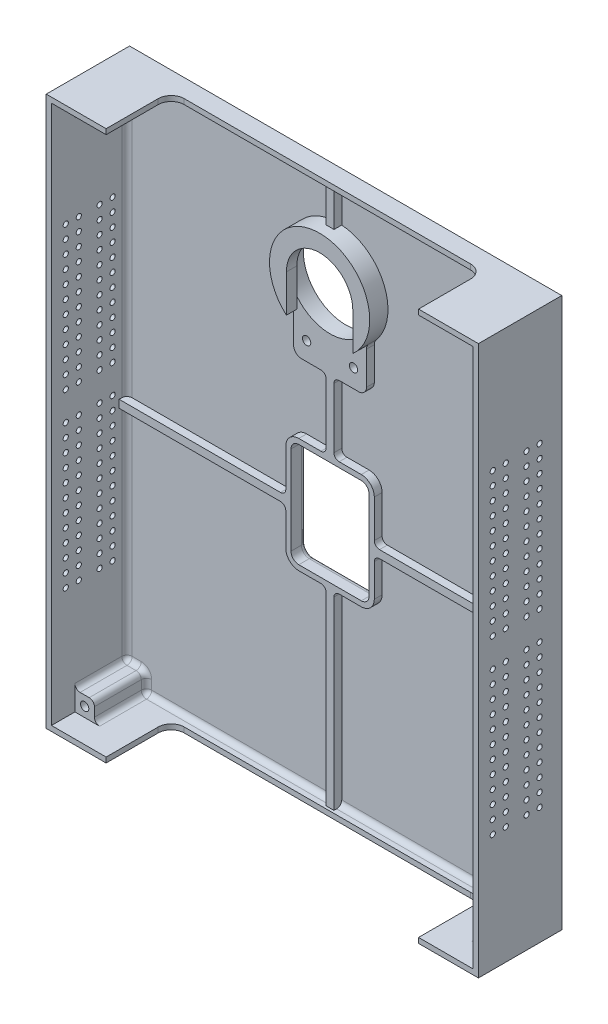
SolidWorks part; units mm, degrees
ref_plane "Front Plane" through (0, 0, 0) normal (0, 0, 1) x (1, 0, 0)
ref_plane "Top Plane" through (0, 0, 0) normal (0, 1, 0) x (1, 0, 0)
ref_plane "Right Plane" through (0, 0, 0) normal (1, 0, 0) x (0, 0, -1)
ref_plane "Plane1" through (0, 0, -1) normal (0, 0, 1) x (1, 0, 0)
sketch "Sketch5" plane through (0, 0, -1) normal (0, 0, 1) x (1, 0, 0)
  line L0 (100, 83.2573) -> (100, -169.2647) construction
  line L2 (17, 83.2573) -> (17, -127.7573)
  line L3 (17, -127.7573) -> (183, -127.7573)
  line L4 (183, 83.2573) -> (183, -127.7573)
  line L5 (17, 83.2573) -> (183, 83.2573)
  circle A0 centre (100, 48.2573) radius 16.25
  point P17 (45, 83.2573)
  dimension "D1" = 166
  dimension "D2" = 83
extrude "Boss-Extrude5" add sketch "Sketch5" along normal blind 3
sketch "Sketch6" plane through (0, 0, 2) normal (0, 0, 1) x (1, 0, 0)
  line L0 (116.25, 48.2573) -> (83.75, 48.2573) construction
  line L2 (86, 35.0451) -> (86, 18.2573)
  line L3 (86, 18.2573) -> (114, 18.2573)
  line L4 (114, 35.0451) -> (114, 18.2573)
  line L5 (100, 48.2573) -> (100, 52.872) construction
  circle A1 centre (100, 48.2573) radius 16.25
  arc A2 (114, 35.0451) -> (86, 35.0451) centre (100, 48.2573) ccw
  circle A6 centre (100, 48.2573) radius 16.25 construction
extrude "Boss-Extrude6" add sketch "Sketch6" along normal blind 3
sketch "Sketch7" plane through (0, 0, 5) normal (0, 0, 1) x (1, 0, 0)
  line L0 (112.75, 33.8351) -> (112.75, 48.2573)
  line L2 (87.25, 48.2573) -> (87.25, 33.8351)
  line L3 (100, 64.5073) -> (100, 48.2573) construction
  line L4 (100, 48.2573) -> (116.25, 48.2573) construction
  arc A8 (112.75, 33.8351) -> (87.25, 33.8351) centre (100, 48.2573) ccw
  circle A9 centre (100, 48.2573) radius 19.25 construction
  circle A10 centre (100, 48.2573) radius 16.25 construction
  circle A12 centre (100, 48.2573) radius 12.75
  arc A13 (112.75, 48.2573) -> (87.25, 48.2573) centre (100, 48.2573) ccw
  dimension "D1" = 1
extrude "Boss-Extrude7" add sketch "Sketch7" along normal blind 4
sketch "Sketch8" plane through (0, 0, 2) normal (0, 0, 1) x (1, 0, 0)
  line L4 (17, -127.7573) -> (183, -127.7573)
  line L5 (183, -127.7573) -> (183, 83.2573)
  line L6 (183, 83.2573) -> (17, 83.2573)
  line L7 (17, 83.2573) -> (17, -127.7573)
  line L8 (17, -127.7573) -> (183, -127.7573)
  line L9 (183, -127.7573) -> (183, 83.2573)
  line L10 (183, 83.2573) -> (17, 83.2573)
  line L11 (17, 83.2573) -> (17, -127.7573)
  line L12 (19, -125.7573) -> (181, -125.7573)
  line L13 (181, -125.7573) -> (181, 81.2573)
  line L14 (181, 81.2573) -> (19, 81.2573)
  line L15 (19, 81.2573) -> (19, -125.7573)
  dimension "D1" = 0
  dimension "D2" = 2
extrude "Boss-Extrude8" add sketch "Sketch8" along normal blind 29
fillet "Fillet2" radius 3 4 edges at (114, 18.2573, 3.5) (114, 35.0451, 3.5) (86, 18.2573, 3.5) (86, 35.0451, 3.5)
sketch "Sketch9" plane through (0, 0, 5) normal (0, 0, 1) x (1, 0, 0)
  line L0 (100, 48.2573) -> (100, 25.2573) construction
  line L1 (91, 25.2573) -> (109, 25.2573) construction
  line L2 (100, 25.2573) -> (100, 23.2329) construction
  circle A0 centre (91, 25.2573) radius 1.6
  circle A1 centre (109, 25.2573) radius 1.6
extrude "Cut-Extrude1" cut sketch "Sketch9" against normal up to surface (6 mm away) up to face at (100, -22.25, -1)
sketch "Sketch12" plane through (183, 0, 0) normal (1, 0, 0) x (0, 0, -1)
  circle A0 centre (-12.5, -16.7427) radius 1
  circle A1 centre (-7.5, -16.7427) radius 1
  circle A2 centre (-7.5, -11.7427) radius 1
  circle A3 centre (-7.5, -6.7427) radius 1
  circle A4 centre (-7.5, -1.7427) radius 1
  circle A5 centre (-7.5, 3.2573) radius 1
  circle A6 centre (-7.5, 8.2573) radius 1
  circle A7 centre (-7.5, 13.2573) radius 1
  circle A8 centre (-7.5, 18.2573) radius 1
  circle A9 centre (-7.5, 23.2573) radius 1
  circle A10 centre (-7.5, 28.2573) radius 1
  circle A11 centre (-7.5, 33.2573) radius 1
  circle A12 centre (-7.5, 38.2573) radius 1
  circle A13 centre (-12.5, -11.7427) radius 1
  circle A14 centre (-12.5, -6.7427) radius 1
  circle A15 centre (-12.5, -1.7427) radius 1
  circle A16 centre (-12.5, 3.2573) radius 1
  circle A17 centre (-12.5, 8.2573) radius 1
  circle A18 centre (-12.5, 13.2573) radius 1
  circle A19 centre (-12.5, 18.2573) radius 1
  circle A20 centre (-12.5, 23.2573) radius 1
  circle A21 centre (-12.5, 28.2573) radius 1
  circle A22 centre (-12.5, 33.2573) radius 1
  circle A23 centre (-12.5, 38.2573) radius 1
  circle A24 centre (-12.5, -82.7573) radius 1
  circle A25 centre (-12.5, -77.7573) radius 1
  circle A26 centre (-12.5, -72.7573) radius 1
  circle A27 centre (-12.5, -67.7573) radius 1
  circle A28 centre (-12.5, -62.7573) radius 1
  circle A29 centre (-12.5, -57.7573) radius 1
  circle A30 centre (-12.5, -52.7573) radius 1
  circle A31 centre (-12.5, -47.7573) radius 1
  circle A32 centre (-12.5, -42.7573) radius 1
  circle A33 centre (-12.5, -37.7573) radius 1
  circle A34 centre (-12.5, -32.7573) radius 1
  circle A35 centre (-7.5, -82.7573) radius 1
  circle A36 centre (-7.5, -77.7573) radius 1
  circle A37 centre (-7.5, -72.7573) radius 1
  circle A38 centre (-7.5, -67.7573) radius 1
  circle A39 centre (-7.5, -62.7573) radius 1
  circle A40 centre (-7.5, -57.7573) radius 1
  circle A41 centre (-7.5, -52.7573) radius 1
  circle A42 centre (-7.5, -47.7573) radius 1
  circle A43 centre (-7.5, -42.7573) radius 1
  circle A44 centre (-7.5, -37.7573) radius 1
  circle A45 centre (-7.5, -32.7573) radius 1
  circle A46 centre (-7.5, -27.7573) radius 1
  circle A47 centre (-12.5, -27.7573) radius 1
  circle A48 centre (-20.5, -27.7573) radius 1
  circle A49 centre (-25.5, -27.7573) radius 1
  circle A50 centre (-25.5, -32.7573) radius 1
  circle A51 centre (-25.5, -37.7573) radius 1
  circle A52 centre (-25.5, -42.7573) radius 1
  circle A53 centre (-25.5, -47.7573) radius 1
  circle A54 centre (-25.5, -52.7573) radius 1
  circle A55 centre (-25.5, -57.7573) radius 1
  circle A56 centre (-25.5, -62.7573) radius 1
  circle A57 centre (-25.5, -67.7573) radius 1
  circle A58 centre (-25.5, -72.7573) radius 1
  circle A59 centre (-25.5, -77.7573) radius 1
  circle A60 centre (-25.5, -82.7573) radius 1
  circle A61 centre (-20.5, -32.7573) radius 1
  circle A62 centre (-20.5, -37.7573) radius 1
  circle A63 centre (-20.5, -42.7573) radius 1
  circle A64 centre (-20.5, -47.7573) radius 1
  circle A65 centre (-20.5, -52.7573) radius 1
  circle A66 centre (-20.5, -57.7573) radius 1
  circle A67 centre (-20.5, -62.7573) radius 1
  circle A68 centre (-20.5, -67.7573) radius 1
  circle A69 centre (-20.5, -72.7573) radius 1
  circle A70 centre (-20.5, -77.7573) radius 1
  circle A71 centre (-20.5, -82.7573) radius 1
  circle A72 centre (-20.5, 38.2573) radius 1
  circle A73 centre (-20.5, 33.2573) radius 1
  circle A74 centre (-20.5, 28.2573) radius 1
  circle A75 centre (-20.5, 23.2573) radius 1
  circle A76 centre (-20.5, 18.2573) radius 1
  circle A77 centre (-20.5, 13.2573) radius 1
  circle A78 centre (-20.5, 8.2573) radius 1
  circle A79 centre (-20.5, 3.2573) radius 1
  circle A80 centre (-20.5, -1.7427) radius 1
  circle A81 centre (-20.5, -6.7427) radius 1
  circle A82 centre (-20.5, -11.7427) radius 1
  circle A83 centre (-25.5, 38.2573) radius 1
  circle A84 centre (-25.5, 33.2573) radius 1
  circle A85 centre (-25.5, 28.2573) radius 1
  circle A86 centre (-25.5, 23.2573) radius 1
  circle A87 centre (-25.5, 18.2573) radius 1
  circle A88 centre (-25.5, 13.2573) radius 1
  circle A89 centre (-25.5, 8.2573) radius 1
  circle A90 centre (-25.5, 3.2573) radius 1
  circle A91 centre (-25.5, -1.7427) radius 1
  circle A92 centre (-25.5, -6.7427) radius 1
  circle A93 centre (-25.5, -11.7427) radius 1
  circle A94 centre (-25.5, -16.7427) radius 1
  circle A95 centre (-20.5, -16.7427) radius 1
  dimension "D1" = 2
  dimension "D2" = 12
extrude "Cut-Extrude4" cut sketch "Sketch12" against normal up to surface (2 mm away) up to face at (181, -22.25, 16.5)
sketch "Sketch13" plane through (0, 0, -1) normal (0, 0, -1) x (-1, 0, 0)
  line L0 (-183, -30.7808) -> (-100, -30.7808) construction
  line L1 (-183, -127.7573) -> (-183, 83.2573) construction
  line L6 (-100, 83.2573) -> (-100, -30.7808) construction
  line L7 (-183, 83.2573) -> (-17, 83.2573) construction
  line L14 (-85, -47.7808) -> (-85, -13.7808)
  line L15 (-88, -10.7808) -> (-112, -10.7808)
  line L16 (-115, -13.7808) -> (-115, -47.7808)
  line L17 (-112, -50.7808) -> (-88, -50.7808)
  circle A1 centre (-100, -30.7808) radius 9 construction
  arc A15 (-88, -50.7808) -> (-85, -47.7808) centre (-88, -47.7808) ccw
  arc A16 (-85, -13.7808) -> (-88, -10.7808) centre (-88, -13.7808) ccw
  arc A17 (-112, -10.7808) -> (-115, -13.7808) centre (-112, -13.7808) ccw
  arc A18 (-115, -47.7808) -> (-112, -50.7808) centre (-112, -47.7808) ccw
extrude "Cut-Extrude5" cut sketch "Sketch13" against normal blind 3
sketch "Sketch14" plane through (17, 0, 0) normal (-1, 0, 0) x (0, 0, 1)
  circle A1 centre (12.5, -82.7573) radius 1
  circle A2 centre (12.5, -82.7573) radius 1
  circle A3 centre (12.5, -16.7427) radius 1
  circle A4 centre (12.5, -16.7427) radius 1
  circle A5 centre (7.5, 18.2573) radius 1
  circle A6 centre (7.5, 18.2573) radius 1
  circle A7 centre (7.5, 13.2573) radius 1
  circle A8 centre (7.5, 13.2573) radius 1
  circle A9 centre (7.5, 8.2573) radius 1
  circle A10 centre (7.5, 8.2573) radius 1
  circle A11 centre (7.5, 3.2573) radius 1
  circle A12 centre (7.5, 3.2573) radius 1
  circle A13 centre (7.5, -1.7427) radius 1
  circle A14 centre (7.5, -1.7427) radius 1
  circle A15 centre (7.5, -6.7427) radius 1
  circle A16 centre (7.5, -6.7427) radius 1
  circle A17 centre (7.5, -11.7427) radius 1
  circle A18 centre (7.5, -11.7427) radius 1
  circle A19 centre (7.5, -16.7427) radius 1
  circle A20 centre (7.5, -16.7427) radius 1
  circle A21 centre (12.5, 3.2573) radius 1
  circle A22 centre (12.5, 3.2573) radius 1
  circle A23 centre (12.5, -1.7427) radius 1
  circle A24 centre (12.5, -1.7427) radius 1
  circle A25 centre (12.5, -6.7427) radius 1
  circle A26 centre (12.5, -6.7427) radius 1
  circle A27 centre (12.5, -11.7427) radius 1
  circle A28 centre (12.5, -11.7427) radius 1
  circle A29 centre (7.5, 38.2573) radius 1
  circle A30 centre (7.5, 38.2573) radius 1
  circle A31 centre (7.5, 33.2573) radius 1
  circle A32 centre (7.5, 33.2573) radius 1
  circle A33 centre (7.5, 28.2573) radius 1
  circle A34 centre (7.5, 28.2573) radius 1
  circle A35 centre (7.5, 23.2573) radius 1
  circle A36 centre (7.5, 23.2573) radius 1
  circle A37 centre (12.5, -77.7573) radius 1
  circle A38 centre (12.5, -77.7573) radius 1
  circle A39 centre (12.5, 38.2573) radius 1
  circle A40 centre (12.5, 38.2573) radius 1
  circle A41 centre (12.5, 33.2573) radius 1
  circle A42 centre (12.5, 33.2573) radius 1
  circle A43 centre (12.5, 28.2573) radius 1
  circle A44 centre (12.5, 28.2573) radius 1
  circle A45 centre (12.5, 23.2573) radius 1
  circle A46 centre (12.5, 23.2573) radius 1
  circle A47 centre (12.5, 18.2573) radius 1
  circle A48 centre (12.5, 18.2573) radius 1
  circle A49 centre (12.5, 13.2573) radius 1
  circle A50 centre (12.5, 13.2573) radius 1
  circle A51 centre (12.5, 8.2573) radius 1
  circle A52 centre (12.5, 8.2573) radius 1
  circle A53 centre (12.5, -37.7573) radius 1
  circle A54 centre (12.5, -37.7573) radius 1
  circle A55 centre (12.5, -42.7573) radius 1
  circle A56 centre (12.5, -42.7573) radius 1
  circle A57 centre (12.5, -47.7573) radius 1
  circle A58 centre (12.5, -47.7573) radius 1
  circle A59 centre (12.5, -52.7573) radius 1
  circle A60 centre (12.5, -52.7573) radius 1
  circle A61 centre (12.5, -57.7573) radius 1
  circle A62 centre (12.5, -57.7573) radius 1
  circle A63 centre (12.5, -62.7573) radius 1
  circle A64 centre (12.5, -62.7573) radius 1
  circle A65 centre (12.5, -67.7573) radius 1
  circle A66 centre (12.5, -67.7573) radius 1
  circle A67 centre (12.5, -72.7573) radius 1
  circle A68 centre (12.5, -72.7573) radius 1
  circle A69 centre (7.5, -52.7573) radius 1
  circle A70 centre (7.5, -52.7573) radius 1
  circle A71 centre (7.5, -57.7573) radius 1
  circle A72 centre (7.5, -57.7573) radius 1
  circle A73 centre (7.5, -62.7573) radius 1
  circle A74 centre (7.5, -62.7573) radius 1
  circle A75 centre (7.5, -67.7573) radius 1
  circle A76 centre (7.5, -67.7573) radius 1
  circle A77 centre (7.5, -72.7573) radius 1
  circle A78 centre (7.5, -72.7573) radius 1
  circle A79 centre (7.5, -77.7573) radius 1
  circle A80 centre (7.5, -77.7573) radius 1
  circle A81 centre (7.5, -82.7573) radius 1
  circle A82 centre (7.5, -82.7573) radius 1
  circle A83 centre (12.5, -32.7573) radius 1
  circle A84 centre (12.5, -32.7573) radius 1
  circle A85 centre (25.5, -27.7573) radius 1
  circle A86 centre (25.5, -27.7573) radius 1
  circle A87 centre (20.5, -27.7573) radius 1
  circle A88 centre (20.5, -27.7573) radius 1
  circle A89 centre (12.5, -27.7573) radius 1
  circle A90 centre (12.5, -27.7573) radius 1
  circle A91 centre (7.5, -27.7573) radius 1
  circle A92 centre (7.5, -27.7573) radius 1
  circle A93 centre (7.5, -32.7573) radius 1
  circle A94 centre (7.5, -32.7573) radius 1
  circle A95 centre (7.5, -37.7573) radius 1
  circle A96 centre (7.5, -37.7573) radius 1
  circle A97 centre (7.5, -42.7573) radius 1
  circle A98 centre (7.5, -42.7573) radius 1
  circle A99 centre (7.5, -47.7573) radius 1
  circle A100 centre (7.5, -47.7573) radius 1
  circle A101 centre (25.5, -67.7573) radius 1
  circle A102 centre (25.5, -67.7573) radius 1
  circle A103 centre (25.5, -62.7573) radius 1
  circle A104 centre (25.5, -62.7573) radius 1
  circle A105 centre (25.5, -57.7573) radius 1
  circle A106 centre (25.5, -57.7573) radius 1
  circle A107 centre (25.5, -52.7573) radius 1
  circle A108 centre (25.5, -52.7573) radius 1
  circle A109 centre (25.5, -47.7573) radius 1
  circle A110 centre (25.5, -47.7573) radius 1
  circle A111 centre (25.5, -42.7573) radius 1
  circle A112 centre (25.5, -42.7573) radius 1
  circle A113 centre (25.5, -37.7573) radius 1
  circle A114 centre (25.5, -37.7573) radius 1
  circle A115 centre (25.5, -32.7573) radius 1
  circle A116 centre (25.5, -32.7573) radius 1
  circle A117 centre (20.5, -52.7573) radius 1
  circle A118 centre (20.5, -52.7573) radius 1
  circle A119 centre (20.5, -47.7573) radius 1
  circle A120 centre (20.5, -47.7573) radius 1
  circle A121 centre (20.5, -42.7573) radius 1
  circle A122 centre (20.5, -42.7573) radius 1
  circle A123 centre (20.5, -37.7573) radius 1
  circle A124 centre (20.5, -37.7573) radius 1
  circle A125 centre (20.5, -32.7573) radius 1
  circle A126 centre (20.5, -32.7573) radius 1
  circle A127 centre (25.5, -82.7573) radius 1
  circle A128 centre (25.5, -82.7573) radius 1
  circle A129 centre (25.5, -77.7573) radius 1
  circle A130 centre (25.5, -77.7573) radius 1
  circle A131 centre (25.5, -72.7573) radius 1
  circle A132 centre (25.5, -72.7573) radius 1
  circle A133 centre (20.5, 33.2573) radius 1
  circle A134 centre (20.5, 33.2573) radius 1
  circle A135 centre (20.5, 38.2573) radius 1
  circle A136 centre (20.5, 38.2573) radius 1
  circle A137 centre (20.5, -82.7573) radius 1
  circle A138 centre (20.5, -82.7573) radius 1
  circle A139 centre (20.5, -77.7573) radius 1
  circle A140 centre (20.5, -77.7573) radius 1
  circle A141 centre (20.5, -72.7573) radius 1
  circle A142 centre (20.5, -72.7573) radius 1
  circle A143 centre (20.5, -67.7573) radius 1
  circle A144 centre (20.5, -67.7573) radius 1
  circle A145 centre (20.5, -62.7573) radius 1
  circle A146 centre (20.5, -62.7573) radius 1
  circle A147 centre (20.5, -57.7573) radius 1
  circle A148 centre (20.5, -57.7573) radius 1
  circle A149 centre (20.5, -6.7427) radius 1
  circle A150 centre (20.5, -6.7427) radius 1
  circle A151 centre (20.5, -1.7427) radius 1
  circle A152 centre (20.5, -1.7427) radius 1
  circle A153 centre (20.5, 3.2573) radius 1
  circle A154 centre (20.5, 3.2573) radius 1
  circle A155 centre (20.5, 8.2573) radius 1
  circle A156 centre (20.5, 8.2573) radius 1
  circle A157 centre (20.5, 13.2573) radius 1
  circle A158 centre (20.5, 13.2573) radius 1
  circle A159 centre (20.5, 18.2573) radius 1
  circle A160 centre (20.5, 18.2573) radius 1
  circle A161 centre (20.5, 23.2573) radius 1
  circle A162 centre (20.5, 23.2573) radius 1
  circle A163 centre (20.5, 28.2573) radius 1
  circle A164 centre (20.5, 28.2573) radius 1
  circle A165 centre (25.5, 8.2573) radius 1
  circle A166 centre (25.5, 8.2573) radius 1
  circle A167 centre (25.5, 13.2573) radius 1
  circle A168 centre (25.5, 13.2573) radius 1
  circle A169 centre (25.5, 18.2573) radius 1
  circle A170 centre (25.5, 18.2573) radius 1
  circle A171 centre (25.5, 23.2573) radius 1
  circle A172 centre (25.5, 23.2573) radius 1
  circle A173 centre (25.5, 28.2573) radius 1
  circle A174 centre (25.5, 28.2573) radius 1
  circle A175 centre (25.5, 33.2573) radius 1
  circle A176 centre (25.5, 33.2573) radius 1
  circle A177 centre (25.5, 38.2573) radius 1
  circle A178 centre (25.5, 38.2573) radius 1
  circle A179 centre (20.5, -11.7427) radius 1
  circle A180 centre (20.5, -11.7427) radius 1
  circle A181 centre (20.5, -16.7427) radius 1
  circle A182 centre (20.5, -16.7427) radius 1
  circle A183 centre (25.5, -16.7427) radius 1
  circle A184 centre (25.5, -16.7427) radius 1
  circle A185 centre (25.5, -11.7427) radius 1
  circle A186 centre (25.5, -11.7427) radius 1
  circle A187 centre (25.5, -6.7427) radius 1
  circle A188 centre (25.5, -6.7427) radius 1
  circle A189 centre (25.5, -1.7427) radius 1
  circle A190 centre (25.5, -1.7427) radius 1
  circle A191 centre (25.5, 3.2573) radius 1
  circle A192 centre (25.5, 3.2573) radius 1
  dimension "D1" = 0
  dimension "D2" = 0
  dimension "D3" = 0
  dimension "D4" = 0
  dimension "D5" = 0
  dimension "D6" = 0
  dimension "D7" = 0
  dimension "D8" = 0
  dimension "D9" = 0
  dimension "D10" = 0
  dimension "D11" = 0
  dimension "D12" = 0
  dimension "D13" = 0
  dimension "D14" = 0
  dimension "D15" = 0
  dimension "D16" = 0
  dimension "D17" = 0
  dimension "D18" = 0
  dimension "D19" = 0
  dimension "D20" = 0
  dimension "D21" = 0
  dimension "D22" = 0
  dimension "D23" = 0
  dimension "D24" = 0
  dimension "D25" = 0
  dimension "D26" = 0
  dimension "D27" = 0
  dimension "D28" = 0
  dimension "D29" = 0
  dimension "D30" = 0
  dimension "D31" = 0
  dimension "D32" = 0
  dimension "D33" = 0
  dimension "D34" = 0
  dimension "D35" = 0
  dimension "D36" = 0
  dimension "D37" = 0
  dimension "D38" = 0
  dimension "D39" = 0
  dimension "D40" = 0
  dimension "D41" = 0
  dimension "D42" = 0
  dimension "D43" = 0
  dimension "D44" = 0
  dimension "D45" = 0
  dimension "D46" = 0
  dimension "D47" = 0
  dimension "D48" = 0
  dimension "D49" = 0
  dimension "D50" = 0
  dimension "D51" = 0
  dimension "D52" = 0
  dimension "D53" = 0
  dimension "D54" = 0
  dimension "D55" = 0
  dimension "D56" = 0
  dimension "D57" = 0
  dimension "D58" = 0
  dimension "D59" = 0
  dimension "D60" = 0
  dimension "D61" = 0
  dimension "D62" = 0
  dimension "D63" = 0
  dimension "D64" = 0
  dimension "D65" = 0
  dimension "D66" = 0
  dimension "D67" = 0
  dimension "D68" = 0
  dimension "D69" = 0
  dimension "D70" = 0
  dimension "D71" = 0
  dimension "D72" = 0
  dimension "D73" = 0
  dimension "D74" = 0
  dimension "D75" = 0
  dimension "D76" = 0
  dimension "D77" = 0
  dimension "D78" = 0
  dimension "D79" = 0
  dimension "D80" = 0
  dimension "D81" = 0
  dimension "D82" = 0
  dimension "D83" = 0
  dimension "D84" = 0
  dimension "D85" = 0
  dimension "D86" = 0
  dimension "D87" = 0
  dimension "D88" = 0
  dimension "D89" = 0
  dimension "D90" = 0
  dimension "D91" = 0
  dimension "D92" = 0
  dimension "D93" = 0
  dimension "D94" = 0
  dimension "D95" = 0
  dimension "D96" = 0
extrude "Cut-Extrude6" cut sketch "Sketch14" against normal up to surface (2 mm away) up to face at (19, -22.25, 16.5)
sketch "Sketch15" plane through (0, -127.7573, 0) normal (0, -1, 0) x (1, 0, 0)
  line L5 (100, -1) -> (100, 31) construction
  line L6 (17, -1) -> (183, -1) construction
  line L7 (17, 31) -> (183, 31) construction
  line L8 (40, 31) -> (160, 31)
  line L9 (40, 31) -> (40, 11)
  line L10 (45, 6) -> (155, 6)
  line L11 (160, 31) -> (160, 11)
  arc A4 (155, 6) -> (160, 11) centre (155, 11) ccw
  arc A5 (40, 11) -> (45, 6) centre (45, 11) ccw
  point P12 (160, 6)
  point P15 (40, 6)
  dimension "D4" = 5
  dimension "D1" = 60
  dimension "D2" = 120
  dimension "D3" = 25
extrude "Cut-Extrude7" cut sketch "Sketch15" against normal up to surface (2 mm away) up to face at (100, -125.7573, 16.5)
sketch "Sketch16" plane through (0, 83.2573, 0) normal (0, 1, 0) x (1, 0, 0)
  line L4 (40, -31) -> (160, -31)
  line L5 (40, -31) -> (160, -31)
  line L6 (160, -31) -> (160, -11)
  line L7 (160, -31) -> (160, -11)
  line L12 (155, -6) -> (45, -6)
  line L13 (155, -6) -> (45, -6)
  line L14 (40, -11) -> (40, -31)
  line L15 (40, -11) -> (40, -31)
  arc A2 (160, -11) -> (155, -6) centre (155, -11) ccw
  arc A3 (160, -11) -> (155, -6) centre (155, -11) ccw
  arc A4 (45, -6) -> (40, -11) centre (45, -11) ccw
  arc A5 (45, -6) -> (40, -11) centre (45, -11) ccw
  dimension "D1" = 0
extrude "Cut-Extrude8" cut sketch "Sketch16" against normal up to surface (2 mm away) up to face at (100, 81.2573, 16.5)
sketch "Sketch18" plane through (0, 0, 2) normal (0, 0, 1) x (1, 0, 0)
  line L1 (19, -125.7573) -> (26.5, -125.7573)
  line L2 (19, -125.7573) -> (19, -118.2573)
  line L3 (19, -118.2573) -> (26.5, -118.2573)
  line L4 (26.5, -125.7573) -> (26.5, -118.2573)
  line L5 (181, -125.7573) -> (173.5, -125.7573)
  line L6 (181, -125.7573) -> (181, -118.2573)
  line L7 (181, -118.2573) -> (173.5, -118.2573)
  line L8 (173.5, -125.7573) -> (173.5, -118.2573)
  line L9 (19, 81.2573) -> (26.5, 81.2573)
  line L10 (19, 81.2573) -> (19, 73.7573)
  line L11 (19, 73.7573) -> (26.5, 73.7573)
  line L12 (26.5, 81.2573) -> (26.5, 73.7573)
  line L13 (181, 81.2573) -> (173.5, 81.2573)
  line L14 (181, 81.2573) -> (181, 73.7573)
  line L15 (181, 73.7573) -> (173.5, 73.7573)
  line L16 (173.5, 81.2573) -> (173.5, 73.7573)
extrude "Boss-Extrude10" add sketch "Sketch18" along normal blind 20
fillet "Fillet3" radius 2 12 edges at (181, 73.7573, 12) (173.5, 73.7573, 12) (173.5, 81.2573, 12) (26.5, 81.2573, 12) (26.5, 73.7573, 12) (19, 73.7573, 12) (19, -118.2573, 12) (26.5, -118.2573, 12) (26.5, -125.7573, 12) (181, -118.2573, 12) (173.5, -118.2573, 12) (173.5, -125.7573, 12)
sketch "Sketch19" plane through (0, 0, 22) normal (0, 0, 1) x (1, 0, 0)
  line L4 (100, -127.7573) -> (100, 83.2573) construction
  line L5 (45, -127.7573) -> (155, -127.7573) construction
  line L6 (155, 83.2573) -> (45, 83.2573) construction
  line L7 (100, -22.25) -> (17, -22.25) construction
  line L8 (17, 83.2573) -> (17, -127.7573) construction
  circle A0 centre (22.75, -122.0073) radius 1.6
  circle A1 centre (177.25, -122.0073) radius 1.6
  circle A2 centre (177.25, 77.5073) radius 1.6
  circle A3 centre (22.75, 77.5073) radius 1.6
extrude "Cut-Extrude9" cut sketch "Sketch19" against normal up to surface (23 mm away) up to face at (100, -30.7808, -1)
fillet "Fillet4" radius 2 24 edges at (180.4142, -117.6715, 2) (177.25, -118.2573, 2) (174.0858, -118.8431, 2) (173.5, -122.0073, 2) (172.9142, -125.1715, 2) (100, -125.7573, 2) (27.0858, -125.1715, 2) (26.5, -122.0073, 2) (25.9142, -118.8431, 2) (22.75, -118.2573, 2) (19.5858, -117.6715, 2) (19, -22.25, 2) (19.5858, 73.1715, 2) (22.75, 73.7573, 2) (25.9142, 74.3431, 2) (26.5, 77.5073, 2) (27.0858, 80.6715, 2) (100, 81.2573, 2) (172.9142, 80.6715, 2) (173.5, 77.5073, 2) (174.0858, 74.3431, 2) (177.25, 73.7573, 2) (180.4142, 73.1715, 2) (181, -22.25, 2)
sketch "Sketch20" plane through (0, 0, 2) normal (0, 0, 1) x (1, 0, 0)
  line L0 (83, -30.2573) -> (83, -13.7808)
  line L1 (155, 83.2573) -> (45, 83.2573) construction
  line L2 (45, -127.7573) -> (155, -127.7573) construction
  line L3 (88, -10.7808) -> (112, -10.7808) construction
  line L4 (101.5, -127.7573) -> (98.5, -127.7573)
  line L5 (101.5, -127.7573) -> (101.5, -52.7808)
  line L6 (101.5, 83.2573) -> (98.5, 83.2573)
  line L7 (98.5, -127.7573) -> (98.5, -52.7808)
  line L8 (115, -13.7808) -> (115, -47.7808) construction
  line L9 (112, -50.7808) -> (88, -50.7808) construction
  line L10 (85, -47.7808) -> (85, -13.7808) construction
  line L11 (88, -10.7808) -> (112, -10.7808)
  line L12 (115, -13.7808) -> (115, -47.7808)
  line L13 (112, -50.7808) -> (88, -50.7808)
  line L14 (85, -47.7808) -> (85, -13.7808)
  line L15 (88, -8.7808) -> (98.5, -8.7808)
  line L16 (117, -13.7808) -> (117, -30.2573)
  line L17 (112, -52.7808) -> (101.5, -52.7808)
  line L18 (83, -47.7808) -> (83, -33.2573)
  line L19 (101.5, -8.7808) -> (112, -8.7808)
  line L20 (183, -127.7573) -> (183, 83.2573) construction
  line L21 (183, -33.2573) -> (117, -33.2573)
  line L22 (183, -33.2573) -> (183, -30.2573)
  line L23 (183, -30.2573) -> (117, -30.2573)
  line L24 (17, -33.2573) -> (17, -30.2573)
  line L25 (17, 83.2573) -> (17, -127.7573) construction
  line L26 (83, -33.2573) -> (17, -33.2573)
  line L28 (98.5, -52.7808) -> (88, -52.7808)
  line L31 (83, -30.2573) -> (17, -30.2573)
  line L32 (98.5, -8.7808) -> (98.5, 18.2573)
  line L33 (112, -52.7808) -> (88, -52.7808) construction
  line L35 (117, -33.2573) -> (117, -47.7808)
  line L37 (101.5, -8.7808) -> (101.5, 18.2573)
  line L38 (117, -13.7808) -> (117, -47.7808) construction
  line L39 (88, -8.7808) -> (112, -8.7808) construction
  line L40 (83, -47.7808) -> (83, -13.7808) construction
  line L42 (89, 18.2573) -> (111, 18.2573) construction
  line L43 (98.5, 18.2573) -> (101.5, 18.2573)
  line L44 (98.5, 64.4379) -> (98.5, 83.2573)
  line L45 (101.5, 64.4379) -> (101.5, 83.2573)
  line L49 (112.75, 48.2573) -> (112.75, 38.1826)
  line L51 (87.25, 38.1826) -> (87.25, 48.2573)
  arc A0 (88, -10.7808) -> (85, -13.7808) centre (88, -13.7808) ccw construction
  arc A1 (115, -13.7808) -> (112, -10.7808) centre (112, -13.7808) ccw construction
  arc A2 (112, -50.7808) -> (115, -47.7808) centre (112, -47.7808) ccw construction
  arc A3 (85, -47.7808) -> (88, -50.7808) centre (88, -47.7808) ccw construction
  arc A4 (88, -10.7808) -> (85, -13.7808) centre (88, -13.7808) ccw
  arc A5 (115, -13.7808) -> (112, -10.7808) centre (112, -13.7808) ccw
  arc A6 (112, -50.7808) -> (115, -47.7808) centre (112, -47.7808) ccw
  arc A7 (85, -47.7808) -> (88, -50.7808) centre (88, -47.7808) ccw
  arc A8 (117, -13.7808) -> (112, -8.7808) centre (112, -13.7808) ccw
  arc A9 (112, -52.7808) -> (117, -47.7808) centre (112, -47.7808) ccw
  arc A10 (83, -47.7808) -> (88, -52.7808) centre (88, -47.7808) ccw
  arc A11 (88, -8.7808) -> (83, -13.7808) centre (88, -13.7808) ccw
  arc A14 (112.75, 48.2573) -> (87.25, 48.2573) centre (100, 48.2573) ccw
  arc A15 (112.75, 38.1826) -> (87.25, 38.1826) centre (100, 48.2573) ccw
  arc A18 (101.5, 64.4379) -> (98.5, 64.4379) centre (100, 48.2573) ccw
  dimension "D1" = 0
  dimension "D3" = 2
extrude "Boss-Extrude11" add sketch "Sketch20" along normal blind 3
fillet "Fillet5" radius 2 10 edges at (98.5, -52.7808, 3.5) (101.5, -52.7808, 3.5) (117, -33.2573, 3.5) (117, -30.2573, 3.5) (83, -33.2573, 3.5) (83, -30.2573, 3.5) (98.5, -8.7808, 3.5) (101.5, -8.7808, 3.5) (98.5, 18.2573, 3.5) (101.5, 18.2573, 3.5)
sketch "Sketch21" plane through (0, 0, -1) normal (0, 0, -1) x (-1, 0, 0)
  circle A0 centre (-109, 25.2573) radius 2.25
  circle A1 centre (-91, 25.2573) radius 2.25
extrude "Cut-Extrude10" cut sketch "Sketch21" against normal blind 3
fillet "Fillet6" radius 2 8 edges at (85.8787, -49.9021, -1) (100, -50.7808, -1) (114.1213, -49.9021, -1) (115, -30.7808, -1) (114.1213, -11.6594, -1) (100, -10.7808, -1) (85.8787, -11.6594, -1) (85, -30.7808, -1)
chamfer "Chamfer1" distance 1.5 angle 45 4 edges at (21.15, 77.5073, -1) (21.15, -122.0073, -1) (175.65, -122.0073, -1) (175.65, 77.5073, -1)
